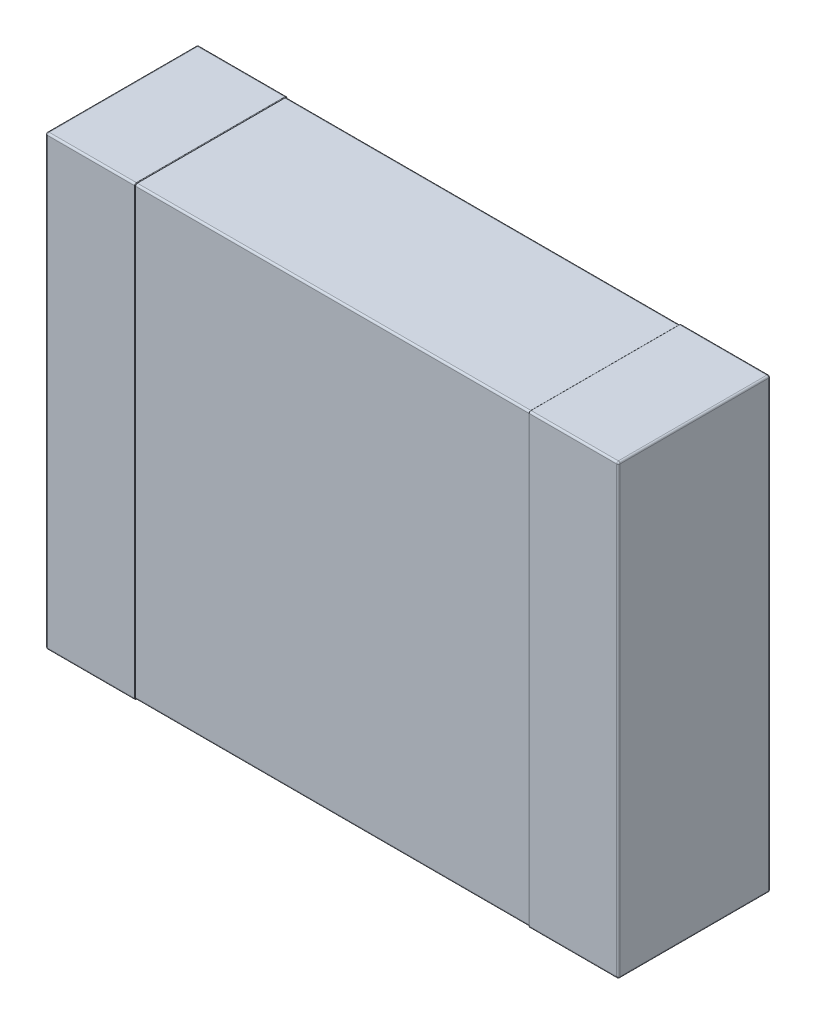
SolidWorks part; units mm, degrees
ref_plane "Top Plane" through (0, 0, 0) normal (0, 0, 1) x (1, 0, 0)
ref_plane "Front Plane" through (0, 0, 0) normal (0, 1, 0) x (1, 0, 0)
ref_plane "Side Plane" through (0, 0, 0) normal (1, 0, 0) x (0, 0, -1)
sketch "Sketch1" plane through (0, 0, 0) normal (0, 0, 1) x (1, 0, 0)
  line L1 (-1.6, 1.25) -> (1.6, 1.25)
  line L2 (-1.6, 1.25) -> (-1.6, -1.25)
  line L3 (-1.6, -1.25) -> (1.6, -1.25)
  line L4 (1.6, 1.25) -> (1.6, -1.25)
  dimension "D1" = 3.2
  dimension "D2" = 1.6
  dimension "D3" = 2.5
  dimension "D4" = 1.25
extrude "All body" add sketch "Sketch1" along normal blind 0.85
sketch "Sketch2" plane through (0, 0, 0) normal (1, 0, 0) x (0, 0, -1)
  line L14 (-0.003, 1.247) -> (-0.847, 1.247)
  line L15 (-0.003, -1.247) -> (-0.003, 1.247)
  line L16 (-0.847, -1.247) -> (-0.003, -1.247)
  line L17 (-0.847, 1.247) -> (-0.847, -1.247)
  line L18 (-0.003, 1.247) -> (-0.847, 1.247)
  line L19 (-0.003, -1.247) -> (-0.003, 1.247)
  line L20 (-0.847, -1.247) -> (-0.003, -1.247)
  line L21 (-0.847, 1.247) -> (-0.847, -1.247)
  dimension "D1" = 0.003
extrude "Cut out the body for pin" cut sketch "Sketch2" against normal blind 1.1 and the other way blind 1.1 flip side to cut
fillet "Body fillet" radius 0.01 4 edges at (0, 1.247, 0.003) (0, 1.247, 0.847) (0, -1.247, 0.003) (0, -1.247, 0.847)
fillet "Pin fillet a" radius 0.01 16 edges at (1.6, -1.25, 0.425) (1.6, 0, 0.85) (1.6, 1.25, 0.425) (1.6, 0, 0) (-1.6, 1.25, 0.425) (-1.6, 0, 0.85) (-1.6, -1.25, 0.425) (-1.6, 0, 0) (1.35, 1.25, 0.85) (1.35, -1.25, 0.85) (1.35, -1.25, 0) (1.35, 1.25, 0) (-1.35, 1.25, 0) (-1.35, -1.25, 0) (-1.35, 1.25, 0.85) (-1.35, -1.25, 0.85)
fillet "Pin fillet b" radius 0.003 16 edges at (1.1, -1.2471, 0.8471) (1.1, -1.25, 0.425) (1.1, -1.2471, 0.0029) (1.1, 0, 0) (1.1, 1.2471, 0.0029) (1.1, 1.25, 0.425) (1.1, 1.2471, 0.8471) (-1.1, -1.2471, 0.8471) (-1.1, -1.25, 0.425) (-1.1, -1.2471, 0.0029) (-1.1, 0, 0) (-1.1, 1.2471, 0.0029) (-1.1, 1.25, 0.425) (-1.1, 1.2471, 0.8471) (1.1, 0, 0.85) (-1.1, 0, 0.85)
